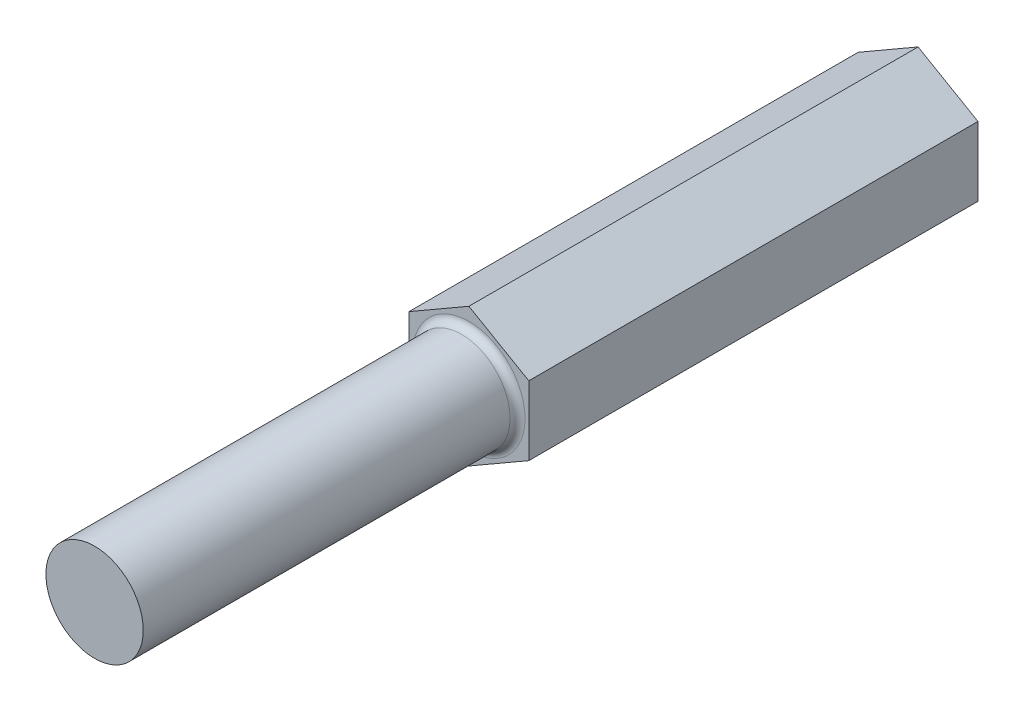
SolidWorks part; units mm, degrees
ref_plane "Plan de face" through (0, 0, 0) normal (0, 0, 1) x (1, 0, 0)
ref_plane "Plan de dessus" through (0, 0, 0) normal (0, 1, 0) x (1, 0, 0)
ref_plane "Plan de droite" through (0, 0, 0) normal (1, 0, 0) x (0, 0, -1)
sketch "Esquisse1" plane through (0, 0, 0) normal (0, 0, 1) x (1, 0, 0)
  line L1 (-4.001, 2.31) -> (-4.001, -2.31)
  line L2 (-4.001, -2.31) -> (0, -4.62)
  line L3 (0, -4.62) -> (4.001, -2.31)
  line L4 (4.001, -2.31) -> (4.001, 2.31)
  line L5 (4.001, 2.31) -> (0, 4.62)
  line L6 (0, 4.62) -> (-4.001, 2.31)
  circle A0 centre (0, 0) radius 4.001 construction
  point P1 (0, 0)
  point P10 (0, 0)
  point P11 (0, 0)
  point P12 (0, -5.3347)
  point P13 (0, 0)
  dimension "D1" = 4.62
extrude "Boss.-Extru.1" add sketch "Esquisse1" along normal blind 30
sketch "Esquisse2" plane through (0, 0, 30) normal (0, 0, 1) x (1, 0, 0)
  circle A0 centre (0, 0) radius 3.25
  dimension "D1" = 6.5
extrude "Boss.-Extru.2" add sketch "Esquisse2" along normal blind 25
fillet "Congé1" radius 0.5 1 edges at (3.25, 0, 30)
